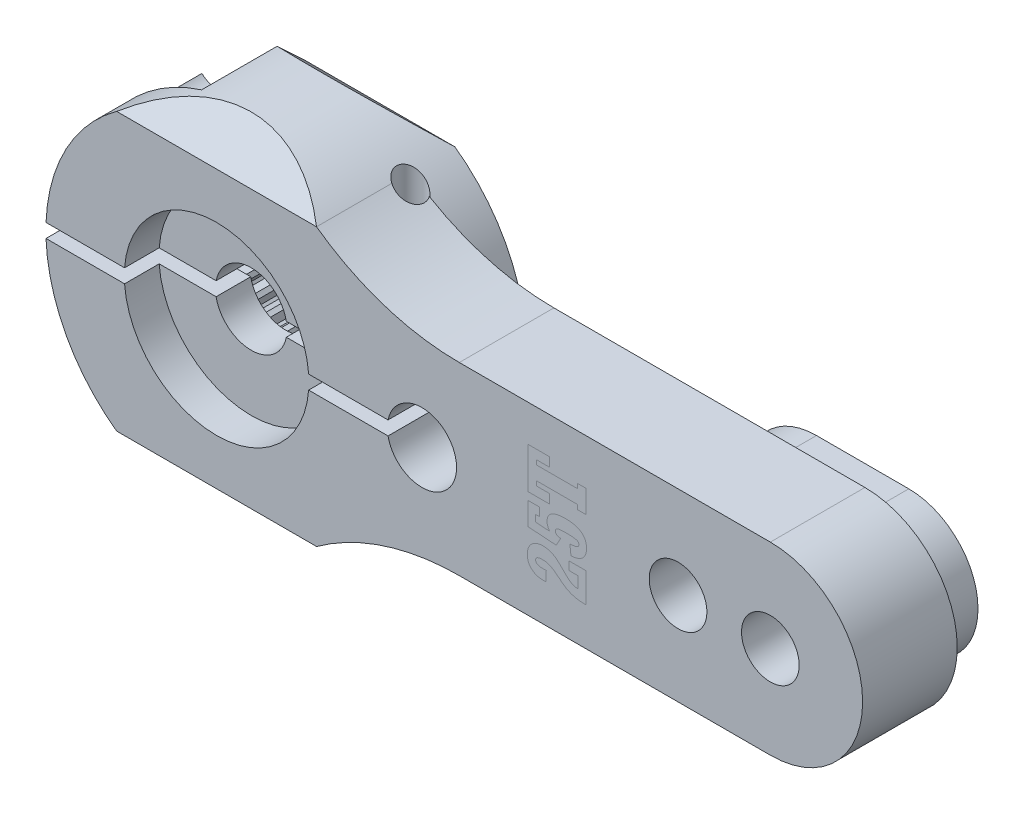
SolidWorks part; units mm, degrees
material "6063-T6"
ref_plane "Front Plane" through (0, 0, 0) normal (0, 0, 1) x (1, 0, 0)
ref_plane "Top Plane" through (0, 0, 0) normal (0, 1, 0) x (1, 0, 0)
ref_plane "Right Plane" through (0, 0, 0) normal (1, 0, 0) x (0, 0, -1)
sketch "Sketch1" plane through (0, 0, 0) normal (0, 0, 1) x (1, 0, 0)
  line L0 (0, 0) -> (20, 0) construction
  line L1 (20, 0) -> (24, 0) construction
  circle A0 centre (0, 0) radius 7.4
  circle A1 centre (0, 0) radius 1.55
  dimension "D1" = 20
  dimension "D3" = 14.8
  dimension "D4" = 3.1
  dimension "D2" = 24
extrude "Boss-Extrude1" add sketch "Sketch1" against normal blind 6
sketch "Sketch2" plane through (0, 0, 0) normal (0, 0, 1) x (1, 0, 0)
  line L0 (24, 4) -> (10.5188, 4)
  line L1 (24, -4) -> (10.5188, -4)
  line L2 (4.3313, -6) -> (4.3313, 6) construction
  circle A0 centre (24, 0) radius 4 construction
  arc A1 (24, 4) -> (24, -4) centre (24, 0) cw
  arc A2 (10.5188, -4) -> (4.3313, -6) centre (10.5188, -14.5714) ccw
  arc A3 (10.5188, 4) -> (4.3313, 6) centre (10.5188, 14.5714) cw
  circle A4 centre (0, 0) radius 7.4 construction
  arc A5 (4.3313, -6) -> (4.3313, 6) centre (0, 0) cw
  circle A6 centre (0, 0) radius 1.55 construction
  circle A7 centre (0, 0) radius 1.55
  dimension "D1" = 8
  dimension "D2" = 12
extrude "Boss-Extrude2" add sketch "Sketch2" against normal blind 4.1
sketch "Sketch3" plane through (0, 0, 0) normal (0, 0, 1) x (1, 0, 0)
  line L0 (20, 0) -> (24, 0) construction
  line L1 (20, 3) -> (24, 3)
  line L2 (20, -3) -> (24, -3)
  arc A0 (20, 3) -> (20, -3) centre (20, 0) ccw
  arc A1 (24, -3) -> (24, 3) centre (24, 0) ccw
  point P4 (22, 0)
  dimension "D1" = 6
extrude "Boss-Extrude3" add sketch "Sketch3" against normal blind 7
sketch "Sketch4" plane through (0, 0, 0) normal (0, 0, 1) x (1, 0, 0)
  circle A0 centre (0, 0) radius 2.65
  dimension "D1" = 5.3
extrude "Cut-Extrude1" cut sketch "Sketch4" against normal through all from offset 3 offset against normal yes
chamfer "Chamfer1" distance 0.45 angle 45 1 edges at (2.65, 0, -6)
sketch "Sketch5" plane through (0, 0, 0) normal (0, 0, 1) x (1, 0, 0)
  line L0 (-0.1007, 2.6481) -> (-0.3203, 3.0331) construction
  line L1 (0.1007, 2.6481) -> (0.3203, 3.0331)
  line L2 (0, 0) -> (0, 2.65) construction
  line L3 (0, 0) -> (0.3321, 2.6291) construction
  line L4 (0.3321, 2.6291) -> (0.3823, 3.0259) construction
  line L5 (0.4441, 3.0175) -> (0.5611, 2.5899)
  line L6 (0, 2.65) -> (0, 3.05) construction
  line L7 (-0.3203, 3.0331) -> (0, 0) construction
  line L8 (0.4441, 3.0175) -> (0, 0) construction
  line L9 (0.3203, 3.0331) -> (0.4011, 3.1748) construction
  line L10 (0.4011, 3.1748) -> (0.4441, 3.0175) construction
  arc A0 (-0.1007, 2.6481) -> (0.1007, 2.6481) centre (0, 0) cw construction
  circle A1 centre (0, 0) radius 2.65 construction
  circle A2 centre (0, 0) radius 3.05 construction
  arc A3 (-0.3203, 3.0331) -> (0.3203, 3.0331) centre (0, 0) cw construction
  arc A4 (0.1007, 2.6481) -> (0.5611, 2.5899) centre (0, 0) cw
  arc A5 (0.3203, 3.0331) -> (0.4441, 3.0175) centre (0, 0) cw
  circle A6 centre (0, 0) radius 3.2 construction
  dimension "D1" = 6.1
  dimension "D2" = 59.4
  dimension "D4" = 6.4
  dimension "D3" = 14.4
extrude "Cut-Extrude2" cut sketch "Sketch5" against normal through all from surface starting at face at (2.65, 0, -3)
pattern_circular "CirPattern1" count 25 over 360 about axis through (0, 0, -6) along (0, 0, 1) of "Cut-Extrude2"
sketch "Sketch6" plane through (0, 0, 0) normal (0, 0, 1) x (1, 0, 0)
  line L0 (4.6, -3) -> (4.6, -12.2913) construction
  line L1 (3.25, -3) -> (5.95, -3)
  line L2 (2.25, -4) -> (2.25, -12.2913)
  line L3 (2.25, -12.2913) -> (6.95, -12.2913)
  line L4 (6.95, -4) -> (6.95, -12.2913)
  line L5 (-6.95, 12.2913) -> (-2.25, 12.2913)
  line L6 (-6.95, 12.2913) -> (-6.95, 4)
  line L7 (-5.95, 3) -> (-3.25, 3)
  line L8 (-2.25, 12.2913) -> (-2.25, 4)
  line L9 (-4.6, 3) -> (-4.6, 12.2913) construction
  arc A0 (5.95, -3) -> (6.95, -4) centre (5.95, -4) cw
  arc A1 (3.25, -3) -> (2.25, -4) centre (3.25, -4) ccw
  arc A2 (-3.25, 3) -> (-2.25, 4) centre (-3.25, 4) ccw
  arc A3 (-6.95, 4) -> (-5.95, 3) centre (-5.95, 4) ccw
  dimension "D1" = 1
  dimension "D2" = 4.7
  dimension "D3" = 4.6
  dimension "D4" = 4.6
  dimension "D5" = 3
  dimension "D6" = 3
extrude "Cut-Extrude3" cut sketch "Sketch6" against normal through all from offset 1.6 offset against normal yes
sketch "Sketch7" plane through (0, 0, 0) normal (0, 1, 0) x (1, 0, 0)
  line L0 (-5.95, 3.8) -> (-3.25, 3.8) construction
  line L1 (-5.95, 6) -> (-5.95, 1.6) construction
  line L2 (-3.25, 6) -> (-3.25, 1.6) construction
  line L3 (3.25, 3.8) -> (5.95, 3.8) construction
  line L4 (3.25, 6) -> (3.25, 1.6) construction
  line L5 (5.95, 6) -> (5.95, 1.6) construction
  circle A0 centre (-4.6, 3.8) radius 0.6
  circle A1 centre (4.6, 3.8) radius 0.6
  dimension "D1" = 1.2
extrude "Cut-Extrude4" cut sketch "Sketch7" against normal through all both and the other way through all
sketch "Sketch8" plane through (0, 0, 0) normal (0, 0, 1) x (1, 0, 0)
  line L0 (0, 0) -> (20, 0) construction
  circle A0 centre (8.9, 0) radius 1.5
  circle A1 centre (20, 0) radius 1.25
  circle A2 centre (24, 0) radius 1.25
  circle A3 centre (0, 0) radius 7.4 construction
  dimension "D1" = 2.5
  dimension "D2" = 3
extrude "Cut-Extrude5" cut sketch "Sketch8" against normal through all
sketch "Sketch9" plane through (0, 0, 0) normal (0, 0, 1) x (1, 0, 0)
  line L1 (-12.0488, 0.3) -> (8.9, 0.3)
  line L2 (-12.0488, 0.3) -> (-12.0488, -0.3)
  line L3 (-12.0488, -0.3) -> (8.9, -0.3)
  line L4 (8.9, 0.3) -> (8.9, -0.3)
  dimension "D1" = 0.6
extrude "Cut-Extrude6" cut sketch "Sketch9" against normal through all both and the other way through all
sketch "Sketch10" plane through (0, 0, 0) normal (1, 0, 0) x (0, 0, -1)
  line L0 (0, 6) -> (0, -6)
  line L1 (0, -6) -> (1.5, -7.4)
  line L2 (1.5, -7.4) -> (4.5, -7.4)
  line L3 (4.5, -7.4) -> (6, -6)
  line L4 (6, -6) -> (6, 6)
  line L5 (6, 6) -> (4.5, 7.4)
  line L6 (4.5, 7.4) -> (1.5, 7.4)
  line L7 (1.5, 7.4) -> (0, 6)
  line L8 (0, 0) -> (6, 0) construction
  line L9 (3, 7.4) -> (3, -7.4) construction
  point P12 (3, 0)
  dimension "D1" = 3
  dimension "D2" = 12
  dimension "D3" = 6
  dimension "D4" = 14.8
  dimension "D5" = 3
extrude "Cut-Extrude-Thin1" cut sketch "Sketch10" against normal through all both and the other way through all thin thin type one direction wall 10
sketch "Sketch11" plane through (0, 0, 0) normal (0, 0, 1) x (1, 0, 0)
  circle A0 centre (0, 0) radius 4
  dimension "D1" = 8
extrude "Cut-Extrude7" cut sketch "Sketch11" against normal blind 1.5
sketch "Sketch12" plane through (0, 0, 0) normal (0, 0, 1) x (1, 0, 0)
  line L0 (16, -2.45) -> (16, 2.45) construction
  line L1 (0, 0) -> (16, 0) construction
  text T0 "25T" font "Rockwell Condensed" height 2.5
  dimension "D1" = 16
  dimension "D2" = 4.9
split line "Split Line1"
ref_axis "Axis1" through (0, 0, 0.3) along (0, 0, -1)
equation "\"D4@Sketch6\"=\"D3@Sketch6\""
equation "\"D6@Sketch6\"=\"D5@Sketch6\""
